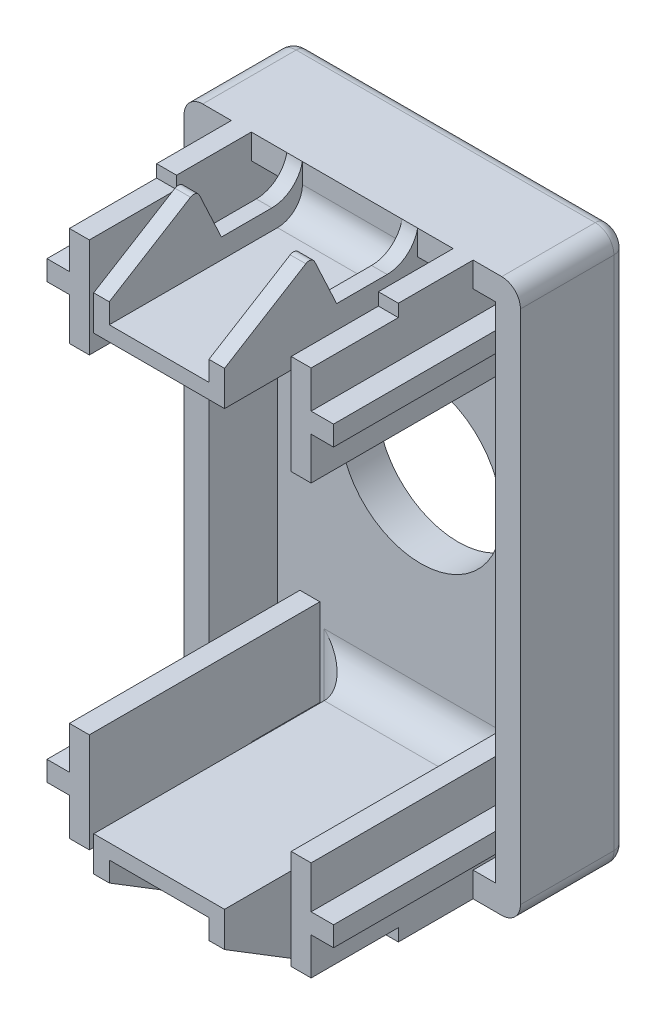
SolidWorks part; units mm, degrees
material "Сталь 3 ГОСТ 535-88"
ref_plane "Спереди" through (0, 0, 0) normal (0, 0, 1) x (1, 0, 0)
ref_plane "Сверху" through (0, 0, 0) normal (0, 1, 0) x (1, 0, 0)
ref_plane "Справа" through (0, 0, 0) normal (1, 0, 0) x (0, 0, -1)
sketch "Эскиз1" plane through (0, 0, 0) normal (0, 0, 1) x (1, 0, 0)
  line L0 (0, 22.2) -> (27, 22.2) construction
  line L1 (0, 0) -> (27, 0)
  line L2 (0, 0) -> (0, 44.4)
  line L3 (0, 44.4) -> (27, 44.4)
  line L4 (27, 0) -> (27, 44.4)
  circle A0 centre (13.5, 22.2) radius 6.5
  dimension "D3" = 13
  dimension "D1" = 27
  dimension "D2" = 44.4
extrude "Бобышка-Вытянуть1" add sketch "Эскиз1" along normal blind 8.5
ref_plane "Плоскость1" through (3, 0, 0) normal (1, 0, 0) x (0, 0, -1)
sketch "Эскиз2" plane through (3, 0, 0) normal (1, 0, 0) x (0, 0, -1)
  line L0 (0, 0) -> (0, 5) construction
  line L2 (0, 45.4) -> (0, 40.4) construction
  line L3 (0, 40.4) -> (0, 5)
  arc A0 (0, 5) -> (0, 40.4) centre (156.145, 22.7) cw
  dimension "D1" = 5
  dimension "D3" = 1
  dimension "D2" = 5
extrude "Вырез-Вытянуть1" cut sketch "Эскиз2" along normal offset from surface (21 mm away) 3 up to face at (27, 22.2, 4.25)
sketch "Эскиз3" plane through (0, 0, 8.5) normal (0, 0, 1) x (1, 0, 0)
  line L0 (25, 2) -> (25, 42.4)
  line L1 (27, 0) -> (0, 0) construction
  line L2 (27, 0) -> (27, 44.4) construction
  line L3 (27, 44.4) -> (0, 44.4) construction
  line L4 (0, 0) -> (0, 44.4) construction
  line L5 (25, 42.4) -> (2, 42.4)
  line L6 (2, 2) -> (2, 42.4)
  line L7 (25, 2) -> (2, 2)
  dimension "D1" = 2
extrude "Вырез-Вытянуть2" cut sketch "Эскиз3" against normal blind 5.5
sketch "Эскиз4" plane through (0, 0, 3) normal (0, 0, 1) x (1, 0, 0)
  line L0 (3.8, 44.4) -> (3.8, 40.4)
  line L1 (25, 42.4) -> (2, 42.4) construction
  line L2 (3.8, 40.4) -> (2, 40.4)
  line L3 (2, 42.4) -> (2, 2) construction
  line L4 (2, 40.4) -> (2, 38.8)
  line L5 (2, 38.8) -> (3.8, 38.8)
  line L6 (3.8, 38.8) -> (3.8, 35.4)
  line L7 (3.8, 35.4) -> (5.4, 35.4)
  line L8 (5.4, 35.4) -> (5.4, 44.4)
  line L10 (5.4, 44.4) -> (3.8, 44.4)
  line L11 (3.8, 38.8) -> (3.8, 40.4) construction
  line L12 (13.5, 42.4) -> (13.5, 2) construction
  line L13 (2, 2) -> (25, 2) construction
  line L14 (25, 22.2) -> (2, 22.2) construction
  line L15 (25, 2) -> (25, 42.4) construction
  line L16 (2, 42.4) -> (2, 2) construction
  line L17 (23.2, 38.8) -> (23.2, 40.4) construction
  line L18 (21.6, 44.4) -> (23.2, 44.4)
  line L19 (21.6, 35.4) -> (21.6, 44.4)
  line L20 (23.2, 35.4) -> (21.6, 35.4)
  line L21 (23.2, 38.8) -> (23.2, 35.4)
  line L22 (25, 38.8) -> (23.2, 38.8)
  line L23 (25, 40.4) -> (25, 38.8)
  line L24 (23.2, 40.4) -> (25, 40.4)
  line L25 (23.2, 44.4) -> (23.2, 40.4)
  line L26 (23.2, 5.6) -> (23.2, 4) construction
  line L27 (3.8, 5.6) -> (3.8, 4) construction
  line L28 (23.2, 0) -> (23.2, 4)
  line L29 (23.2, 4) -> (25, 4)
  line L30 (25, 4) -> (25, 5.6)
  line L31 (25, 5.6) -> (23.2, 5.6)
  line L32 (23.2, 5.6) -> (23.2, 9)
  line L33 (23.2, 9) -> (21.6, 9)
  line L34 (21.6, 9) -> (21.6, 0)
  line L35 (21.6, 0) -> (23.2, 0)
  line L36 (5.4, 0) -> (3.8, 0)
  line L37 (5.4, 9) -> (5.4, 0)
  line L38 (3.8, 9) -> (5.4, 9)
  line L39 (3.8, 5.6) -> (3.8, 9)
  line L40 (2, 5.6) -> (3.8, 5.6)
  line L41 (2, 4) -> (2, 5.6)
  line L42 (3.8, 4) -> (2, 4)
  line L43 (3.8, 0) -> (3.8, 4)
  line L44 (27, 44.4) -> (0, 44.4) construction
  dimension "D1" = 1.6
  dimension "D2" = 1.6
  dimension "D3" = 4
  dimension "D4" = 9
  dimension "D5" = 1.8
extrude "Бобышка-Вытянуть2" add sketch "Эскиз4" along normal blind 18.5
ref_plane "Плоскость2" through (13.5, 0, 0) normal (-1, 0, 0) x (0, 0, 1)
sketch "Эскиз6" plane through (13.5, 0, 0) normal (-1, 0, 0) x (0, 0, 1)
  line L0 (3, 2) -> (3, 4.8)
  line L1 (3, 9) -> (3, 2) construction
  line L2 (3, 4.8) -> (24, 4.8)
  line L3 (24, 4.8) -> (24, 2)
  line L4 (24, 2) -> (17, -2.3)
  line L5 (17, -2.3) -> (15, 2)
  line L6 (15, 2) -> (3, 2)
  line L7 (15, 2) -> (24, 2) construction
  line L8 (0, 22.2) -> (24, 22.2) construction
  line L9 (0, 0) -> (0, 44.4) construction
  line L10 (15, 42.4) -> (24, 42.4) construction
  line L11 (15, 42.4) -> (3, 42.4)
  line L12 (17, 46.7) -> (15, 42.4)
  line L13 (24, 42.4) -> (17, 46.7)
  line L14 (24, 39.6) -> (24, 42.4)
  line L15 (3, 39.6) -> (24, 39.6)
  line L16 (3, 42.4) -> (3, 39.6)
  dimension "D1" = 2.8
  dimension "D2" = 12
  dimension "D3" = 21
  dimension "D4" = 12
  dimension "D5" = 14
  dimension "D6" = 14
  dimension "D7" = 24.5
  dimension "D8" = 24.5
extrude "Бобышка-Вытянуть3" add sketch "Эскиз6" along normal blind 5.25 and the other way blind 5.25
sketch "Эскиз7" plane through (3.8, 0, 0) normal (-1, 0, 0) x (0, 0, 1)
  line L0 (21.5, 4) -> (21.5, 0) construction
  line L1 (21.5, 44.4) -> (14.5, 44.4)
  line L2 (21.5, 44.4) -> (21.5, 43.4)
  line L3 (21.5, 43.4) -> (14.5, 43.4)
  line L4 (14.5, 44.4) -> (14.5, 43.4)
  line L5 (21.5, 0) -> (14.5, 0)
  line L6 (21.5, 0) -> (21.5, 1)
  line L7 (21.5, 1) -> (14.5, 1)
  line L8 (14.5, 0) -> (14.5, 1)
  line L9 (21.5, 0) -> (8.5, 0) construction
  dimension "D1" = 1
  dimension "D2" = 7
  dimension "D3" = 1
  dimension "D4" = 7
extrude "Вырез-Вытянуть3" cut sketch "Эскиз7" against normal blind 3
sketch "Эскиз8" plane through (23.2, 0, 0) normal (1, 0, 0) x (0, 0, -1)
  line L0 (-21.5, 44.4) -> (-8.5, 44.4) construction
  line L1 (-21.5, 0) -> (-14.5, 0)
  line L2 (-21.5, 0) -> (-21.5, 1)
  line L3 (-21.5, 1) -> (-14.5, 1)
  line L4 (-14.5, 0) -> (-14.5, 1)
  line L5 (-21.5, 44.4) -> (-14.5, 44.4)
  line L6 (-21.5, 44.4) -> (-21.5, 43.4)
  line L7 (-21.5, 43.4) -> (-14.5, 43.4)
  line L8 (-14.5, 44.4) -> (-14.5, 43.4)
  dimension "D1" = 1
  dimension "D2" = 1
  dimension "D3" = 7
  dimension "D4" = 7
extrude "Вырез-Вытянуть4" cut sketch "Эскиз8" against normal blind 3
sketch "Эскиз9" plane through (0, 0, 24) normal (0, 0, 1) x (1, 0, 0)
  line L0 (13.5, 2) -> (13.5, -3.5037) construction
  line L1 (18.75, 2) -> (8.25, 2) construction
  line L2 (13.5, 4.675) -> (13.5, -4.675) construction
  line L3 (18.75, 4.8) -> (8.25, 4.8) construction
  line L4 (17.5, 3.6) -> (9.5, 3.6)
  line L5 (17.5, 3.6) -> (17.5, -10.6074)
  line L6 (17.5, -10.6074) -> (9.5, -10.6074)
  line L7 (9.5, 3.6) -> (9.5, -10.6074)
  line L8 (17.5, 3.6) -> (9.5, -10.6074) construction
  line L9 (17.5, -10.6074) -> (9.5, 3.6) construction
  line L10 (0, 22.2) -> (-5.4157, 22.2) construction
  line L11 (0, 44.4) -> (0, 0) construction
  line L12 (17.5, 55.0074) -> (9.5, 40.8) construction
  line L13 (17.5, 40.8) -> (9.5, 55.0074) construction
  line L14 (13.5, 42.4) -> (13.5, 47.9037) construction
  line L15 (9.5, 40.8) -> (9.5, 55.0074)
  line L16 (17.5, 55.0074) -> (9.5, 55.0074)
  line L17 (17.5, 40.8) -> (17.5, 55.0074)
  line L18 (17.5, 40.8) -> (9.5, 40.8)
  dimension "D1" = 8
  dimension "D2" = 1.2
extrude "Вырез-Вытянуть5" cut sketch "Эскиз9" against normal up to surface (15.5 mm away) up to face at (2.2667, 22.2, 8.5)
fillet "Скругление1" radius 1.5 4 edges at (0, 0, 4.25) (27, 0, 4.25) (0, 44.4, 4.25) (27, 44.4, 4.25)
fillet "Скругление3" radius 2.5 10 edges at (8.25, 3.4, 3) (18.75, 3.4, 3) (18.75, 41, 3) (8.25, 41, 3) (13.5, 39.6, 3) (18.125, 42.4, 8.5) (8.875, 42.4, 8.5) (13.5, 4.8, 3) (8.875, 2, 8.5) (18.125, 2, 8.5)
sketch "Эскиз10" plane through (0, 0, 0) normal (0, 0, -1) x (-1, 0, 0)
  line L1 (-2.0478, 41.9069) -> (-24.9298, 41.9069)
  line L2 (-2.0478, 41.9069) -> (-2.0478, 3.4123)
  line L3 (-2.0478, 3.4123) -> (-24.9298, 3.4123)
  line L4 (-24.9298, 41.9069) -> (-24.9298, 3.4123)
  circle A0 centre (-13.5, 22.2) radius 6.5
  dimension "D1" = 13
extrude "Бобышка-Вытянуть4" add sketch "Эскиз10" against normal blind 3
fillet "Скругление4" radius 0.5 4 edges at (18.125, 46.7, 17) (8.875, 46.7, 17) (18.125, -2.3, 17) (8.875, -2.3, 17)
fillet "Скругление5" radius 1 8 edges at (0.4393, 0.4393, 0) (0, 22.2, 0) (0.4393, 43.9607, 0) (13.5, 44.4, 0) (26.5607, 43.9607, 0) (27, 22.2, 0) (26.5607, 0.4393, 0) (13.5, 0, 0)
fillet "Скругление6" radius 2 2 edges at (13.5, 3.6, 8.5) (13.5, 40.8, 8.5)
